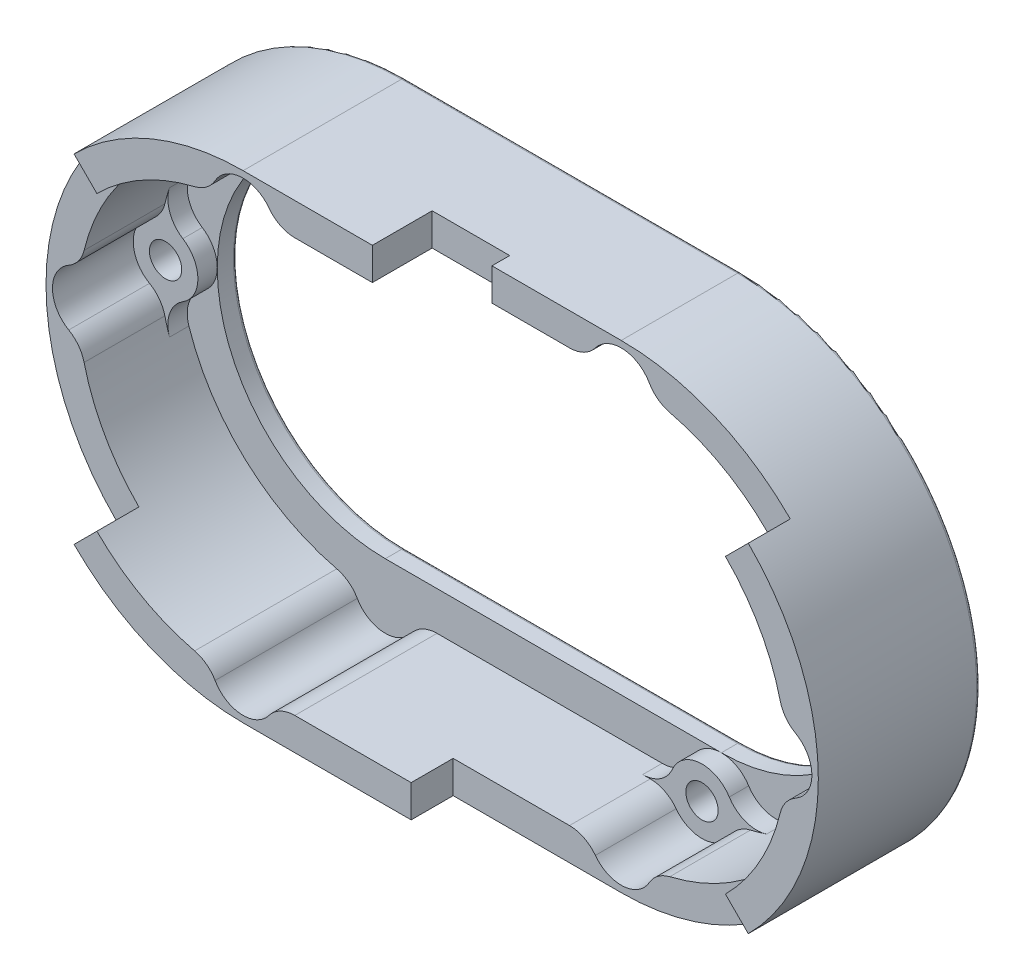
SolidWorks part; units mm, degrees
ref_plane "Front Plane" through (0, 0, 0) normal (0, 0, 1) x (1, 0, 0)
ref_plane "Top Plane" through (0, 0, 0) normal (0, 1, 0) x (1, 0, 0)
ref_plane "Right Plane" through (0, 0, 0) normal (1, 0, 0) x (0, 0, -1)
sketch "Sketch1" plane through (0, 0, 0) normal (0, 0, 1) x (1, 0, 0)
  line L0 (0, 0) -> (52, 0) construction
  line L1 (0, 37) -> (52, 37)
  line L2 (0, -37) -> (52, -37)
  line L3 (0, 0) -> (52, 0) construction
  line L4 (0, 26) -> (52, 26)
  line L5 (0, -26) -> (52, -26)
  line L6 (0, 32) -> (52, 32)
  line L7 (0, -32) -> (52, -32)
  line L8 (0, 26) -> (0, -26) construction
  line L9 (26, 0) -> (26, -26) construction
  line L11 (-36, 0) -> (-37, 0) construction
  arc A0 (0, 37) -> (0, -37) centre (0, 0) ccw
  arc A1 (52, -37) -> (52, 37) centre (52, 0) ccw
  arc A2 (0, 26) -> (0, -26) centre (0, 0) ccw
  arc A3 (52, -26) -> (52, 26) centre (52, 0) ccw
  arc A4 (52, -32) -> (52, 32) centre (52, 0) ccw
  arc A5 (0, 32) -> (0, -32) centre (0, 0) ccw
  circle A6 centre (-31, 0) radius 5
  circle A7 centre (83, 0) radius 5
  circle A8 centre (-31, 0) radius 2.5
  circle A10 centre (52, -31) radius 2.5
  circle A11 centre (52, -31) radius 5
  circle A13 centre (21, 0) radius 5 [skipped]
  circle A14 centre (52, 31) radius 2.5
  circle A15 centre (52, 31) radius 5
  circle A16 centre (0, -31) radius 5
  circle A17 centre (0, 31) radius 5
  point P3 (26, 0)
  point P8 (26, 0)
  point P45 (52, 0)
  dimension "D5" = 52
  dimension "D2" = 1
  dimension "D4" = 5
  dimension "D1" = 6
  dimension "D3" = 11
  dimension "D6" = 4
  dimension "boxInteriorDiam" = 64
extrude "Boss-Extrude1" add sketch "Sketch1" along normal blind 25 contours L2 A1 L1 A0 A17 L6 A15 A4 A7 A11 L7 A16 A5 A6 region at (26, 35.5388, 0)
extrude "Boss-Extrude2" add sketch "Sketch1<3>" along normal blind 3 contours A17 L4 A15 L6 | A5 A17 L6 | A17 A5 A6 A2 | A8 A5 A6 | A5 A8 | A16 A2 A6 A5 | A16 A5 L7 | A16 L7 A11 L5 | A10 L7 A4 | A11 L7 A10 A4 | A3 A11 A4 A7 | A7 A4 | A4 A15 A3 A7 | A15 A4 A14 L6 | A14 A4 L6 | A15 L6 A14 A4 | A14 L6 A4 | L2 A1 L1 A0 A17 L6 A15 A4 A7 A11 L7 A16 A5 A6 | L6 A17 A5 | A8 A5 A6 | A5 A8 | A11 A4 A10 L7 | A10 A4 L7 | A7 A4 | A5 A16 L7 region at (26, 35.5388, 0) region at (26, 28.9238, 0) region at (0.0478, 29.3749, 0) region at (-19.1191, 19.1191, 0) region at (71.1191, 19.1191, 0) region at (48.2173, 27.9115, 0) region at (-27.7652, -3.6589, 0) region at (-19.1191, -19.1191, 0) region at (-0.0775, 33.6344, 0) region at (71.1191, -19.1191, 0) region at (81.3421, 0, 0) region at (52.0886, 33.8404, 0) region at (26, -28.9238, 0) region at (0.0478, -29.3749, 0) region at (-33.797, 0, 0) region at (55.4531, -27.5469, 0) region at (85.5985, 0, 0) region at (52.0221, 32.6105, 0) region at (51.9924, 30.4471, 0) region at (-0.0775, -33.6344, 0) region at (-30.4403, 0, 0) region at (-32.6025, 0, 0) region at (52.0886, -33.8404, 0) region at (51.9924, -30.4471, 0) region at (52.0221, -32.6105, 0)
sketch "Sketch1<3>" plane through (0, 0, 0) normal (0, 0, 1) x (1, 0, 0) same geometry as "Sketch1"
sketch "Sketch2" plane through (0, 37, 0) normal (0, 1, 0) x (1, 0, 0)
  line L0 (0, -25) -> (52, -25) construction
  line L1 (32, -34.25) -> (20, -34.25)
  line L2 (32, -34.25) -> (32, -15.75)
  line L3 (32, -15.75) -> (20, -15.75)
  line L4 (20, -34.25) -> (20, -15.75)
  line L5 (32, -34.25) -> (20, -15.75) construction
  line L6 (32, -15.75) -> (20, -34.25) construction
  point P0 (26, -25)
  dimension "D1" = 12
  dimension "D2" = 18.5
extrude "Cut-Extrude1" cut sketch "Sketch2" against normal up to surface (5 mm away) up to face at (26, 32, 14)
extrude "Boss-Extrude3" add sketch "Sketch1<4>" along normal blind 3 from surface contours A5 A8 | A8 A5 A6 | A15 A4 A14 L6 | A15 L6 A14 A4 | A11 L7 A10 A4 | A11 A4 A10 L7 region at (48.2173, 27.9115, 0) region at (-27.7652, -3.6589, 0) region at (52.0886, 33.8404, 0) region at (-33.797, 0, 0) region at (55.4531, -27.5469, 0) region at (52.0886, -33.8404, 0) starting at face at (26, 0, 3)
sketch "Sketch1<4>" plane through (0, 0, 0) normal (0, 0, 1) x (1, 0, 0) same geometry as "Sketch1"
fillet "Fillet2" radius 5 6 edges at (-31.6129, -4.9623, 4.5) (-31.6129, 4.9623, 4.5) (56.9623, -31.6129, 4.5) (47.101, -32, 4.5) (56.9623, 31.6129, 4.5) (47.101, 32, 4.5)
fillet "Fillet3" radius 5 12 edges at (83.6129, -4.9623, 14) (83.6129, 4.9623, 14) (-31.6129, -4.9623, 15.5) (-31.6129, 4.9623, 15.5) (56.9623, -31.6129, 15.5) (47.101, -32, 15.5) (56.9623, 31.6129, 15.5) (47.101, 32, 15.5) (4.899, -32, 14) (-4.9623, -31.6129, 14) (4.899, 32, 14) (-4.9623, 31.6129, 14)
fillet "Fillet1" radius 0.5 8 edges at (26, -26, 0) (-26, 0, 0) (26, 26, 0) (78, 0, 0) (89, 0, 0) (26, 37, 0) (-37, 0, 0) (26, -37, 0)
extrude "Cut-Extrude3" cut sketch "Sketch1<6>" against normal blind 1.5 from surface contours A8 | A14 | A10 starting at face at (4.4532, -24.3246, 3)
sketch "Sketch1<6>" plane through (0, 0, 0) normal (0, 0, 1) x (1, 0, 0) same geometry as "Sketch1"
sketch "Sketch3" plane through (0, 0, 25) normal (0, 0, 1) x (1, 0, 0)
  line L0 (0, 0) -> (-38.2372, 38.2372)
  line L1 (0, 0) -> (52, 0)
  line L2 (26, -48.8901) -> (26, 48.8901)
  line L3 (52, 0) -> (90.2372, 38.2372)
  line L4 (52, 0) -> (90.2372, -38.2372)
  line L5 (0, 0) -> (-38.2372, -38.2372)
  line L6 (-38.2372, 38.2372) -> (-38.2372, -38.2372)
  line L7 (90.2372, 38.2372) -> (90.2372, -38.2372)
  line L8 (-38.2372, 38.2372) -> (26, 48.8901)
  line L9 (90.2372, 38.2372) -> (26, 48.8901)
  line L10 (-38.2372, -38.2372) -> (26, -48.8901)
  line L11 (90.2372, -38.2372) -> (26, -48.8901)
  arc A0 (52, -37) -> (52, 37) centre (52, 0) ccw construction
  point P13 (26, 0)
  arc M9 (83.1072, -7.506) -> (59.506, -31.1072) centre (52, 0) cw
  arc M10 (59.506, -31.1072) -> (56.3394, -33.4839) centre (60.6788, -35.9677) ccw
  arc M11 (56.3394, -33.4839) -> (48, -34) centre (52, -31) cw
  arc M12 (48, -34) -> (44, -32) centre (44, -37) ccw
  line M13 (44, -32) -> (8, -32)
  arc M17 (-7.506, -31.1072) -> (-31.1072, -7.506) centre (0, 0) cw
  arc M18 (-31.1072, -7.506) -> (-33.4839, -4.3394) centre (-35.9677, -8.6788) ccw
  arc M19 (-33.4839, -4.3394) -> (-33.4839, 4.3394) centre (-31, 0) cw
  arc M20 (-33.4839, 4.3394) -> (-31.1072, 7.506) centre (-35.9677, 8.6788) ccw
  arc M21 (-31.1072, 7.506) -> (-7.506, 31.1072) centre (0, 0) cw
  arc M28 (0, 37) -> (0, -37) centre (0, 0) ccw
  line M29 (0, -37) -> (52, -37)
  arc M30 (52, -37) -> (52, 37) centre (52, 0) ccw
  line M31 (52, 37) -> (32, 37)
  line M32 (32, 37) -> (32, 32)
  line M33 (32, 32) -> (44, 32)
  arc M34 (44, 32) -> (48, 34) centre (44, 37) ccw
  arc M35 (48, 34) -> (56.3394, 33.4839) centre (52, 31) cw
  arc M36 (56.3394, 33.4839) -> (59.506, 31.1072) centre (60.6788, 35.9677) ccw
  arc M37 (59.506, 31.1072) -> (83.1072, 7.506) centre (52, 0) cw
  dimension "D1" = 135
extrude "Cut-Extrude4" cut sketch "Sketch3" against normal blind 6.5 contours L5 L0 M17 M18 M19 M20 M21 M28 | L3 M37 M30 M31 M32 M33 M34 M35 M36 | L4 L2 M9 M10 M11 M12 M13 M29 M30 region at (-28.3842, 15.9173, 25) region at (35, -32.5411, 25) region at (67.8884, 28.3326, 25)
equation "\"speakerCenterDist\" = 40"
equation "\"speakerDiam\" = 50"
equation "\"boxInteriorDiam\" = 64"
